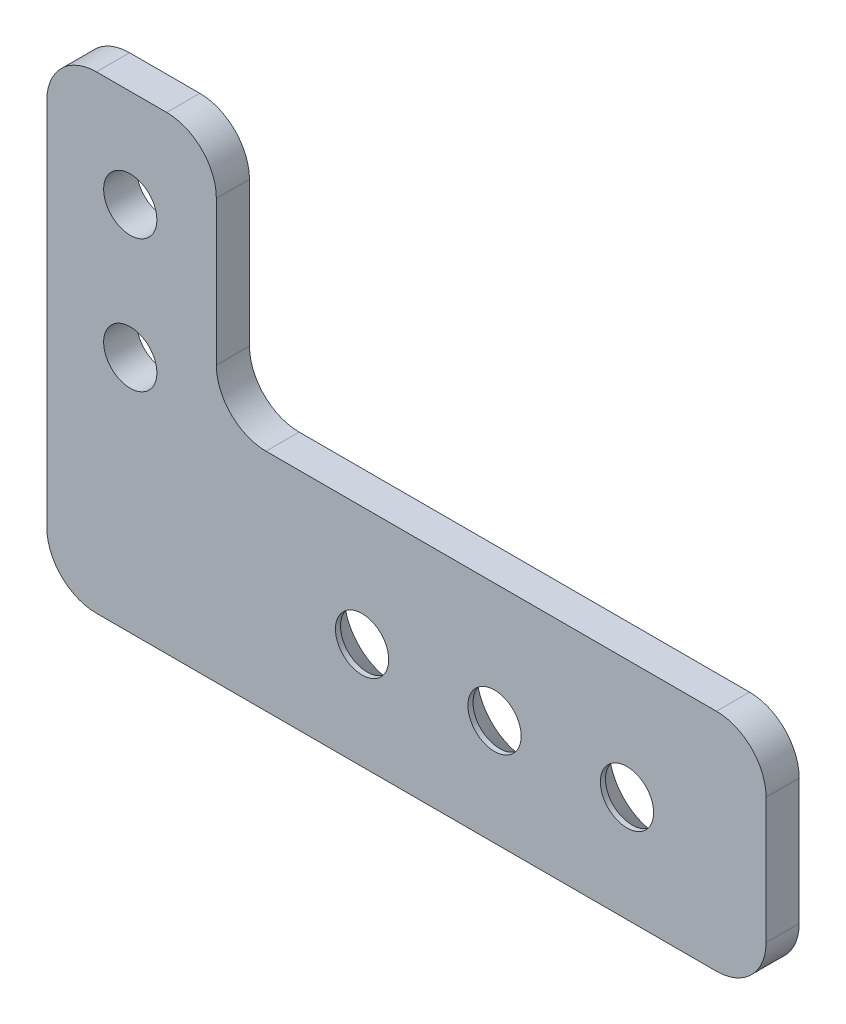
SolidWorks part; units mm, degrees
material "6061-T6 (SS)"
ref_plane "Front Plane" through (0, 0, 0) normal (0, 0, 1) x (1, 0, 0)
ref_plane "Top Plane" through (0, 0, 0) normal (0, 1, 0) x (1, 0, 0)
ref_plane "Right Plane" through (0, 0, 0) normal (1, 0, 0) x (0, 0, -1)
sketch "Sketch1" plane through (0, 0, 0) normal (0, 0, 1) x (1, 0, 0)
  line L0 (38.4175, -11.049) -> (-30.5435, -11.049) construction
  line L1 (-38.4175, -23.749) -> (38.4175, -23.749)
  line L2 (-38.4175, -23.749) -> (-38.4175, 23.749)
  line L3 (-38.4175, 23.749) -> (38.4175, 23.749)
  line L4 (38.4175, -23.749) -> (38.4175, 23.749)
  line L5 (-38.4175, -23.749) -> (38.4175, 23.749) construction
  line L6 (-38.4175, 23.749) -> (38.4175, -23.749) construction
  line L7 (38.4175, 23.749) -> (-14.2875, 23.749)
  line L8 (38.4175, 23.749) -> (38.4175, 0.381)
  line L9 (38.4175, 0.381) -> (-14.2875, 0.381)
  line L10 (-14.2875, 23.749) -> (-14.2875, 0.381)
  line L11 (-38.4175, -23.749) -> (-30.5435, -23.749)
  line L12 (-38.4175, -23.749) -> (-38.4175, 23.749)
  line L13 (-38.4175, 23.749) -> (-30.5435, 23.749)
  line L14 (-30.5435, -23.749) -> (-30.5435, 23.749)
  line L15 (-30.5435, -23.749) -> (38.4175, -23.749)
  line L16 (-30.5435, -23.749) -> (-30.5435, -21.209)
  line L17 (-30.5435, -21.209) -> (38.4175, -21.209)
  line L18 (38.4175, -23.749) -> (38.4175, -21.209)
  line L19 (-30.5435, 23.876) -> (-14.2875, 23.876) construction
  circle A0 centre (-22.5425, -11.049) radius 2.5527
  circle A1 centre (-22.5425, 1.651) radius 2.5527
  circle A2 centre (-22.5425, 14.351) radius 2.5527
  point P0 (0, 0)
  point P22 (25.0825, -11.049)
  point P23 (-0.3175, -11.049)
  point P24 (12.3825, -11.049)
  dimension "D7" = 5.1054
  dimension "D1" = 76.835
  dimension "D2" = 47.498
  dimension "D3" = 24.13
  dimension "D4" = 24.13
  dimension "D5" = 7.874
  dimension "D6" = 47.498
  dimension "D8" = 13.335
  dimension "D9" = 12.7
  dimension "D10" = 12.7
  dimension "D11" = 12.7
  dimension "D12" = 9.525
  dimension "D13" = 12.7
  dimension "D14" = 12.7
  dimension "D15" = 8.001
  dimension "D16" = 2.54
extrude "Boss-Extrude1" add sketch "Sketch1" along normal blind 3.175 contours L14 L17 L4 L9 L10 L3 A2 A1 A0 | A0 region at (-0.7021, -6.0993, 0) region at (-22.5425, -11.049, 0)
fillet "Fillet1" radius 4.7625 6 edges at (-30.5435, 23.749, 1.5875) (-14.2875, 23.749, 1.5875) (-14.2875, 0.381, 1.5875) (38.4175, 0.381, 1.5875) (38.4175, -21.209, 1.5875) (-30.5435, -21.209, 1.5875)
hole_wizard "CSK for #10 Flat Head Machine Screw3" positions "Sketch6" profile "Sketch7" countersink size "#10" standard "ANSI Inch" end condition through all
sketch "Sketch6" plane through (0, 0, 0) normal (0, 0, -1) x (-1, 0, 0)
  point P0 (-25.0825, -11.049)
  point P3 (-12.3825, -11.049)
  point P6 (0.3175, -11.049)
sketch "Sketch7" plane through (25.0825, -11.049, 0) normal (1, 0, 0) x (0, 1, 0)
  line L0 (0, 0) -> (0, 3.175)
  line L1 (0, 3.175) -> (2.5527, 3.175)
  line L2 (2.5527, 3.175) -> (2.5527, 2.6882)
  line L3 (2.5527, 2.6882) -> (4.8895, 0)
  line L5 (4.8895, 0) -> (0, 0)
  line L6 (-2.5527, 2.6882) -> (-4.8895, 0) construction
  line L11 (0, -6.35) -> (0, 107.95) construction
  dimension "Thru Hole Dia." = 5.1054
  dimension "Thru Hole Depth" = 3.175
  dimension "Near C'Sink Dia." = 9.779
  dimension "Near C'Sink Angle" = 82
